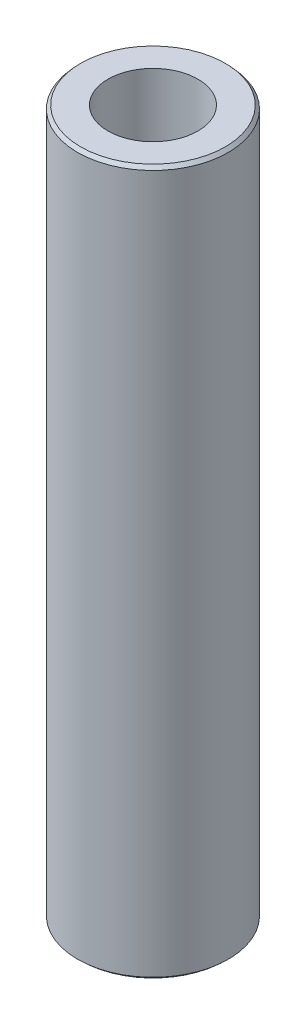
SolidWorks part; units mm, degrees
ref_plane "Front Plane" through (0, 0, 0) normal (0, 0, 1) x (1, 0, 0)
ref_plane "Top Plane" through (0, 0, 0) normal (0, 1, 0) x (1, 0, 0)
ref_plane "Right Plane" through (0, 0, 0) normal (1, 0, 0) x (0, 0, -1)
sketch "Sketch1" plane through (0, 0, 0) normal (0, 1, 0) x (1, 0, 0)
  circle A0 centre (0, 0) radius 15
  dimension "SHAFT_OD" = 30
extrude "Boss-Extrude1" add sketch "Sketch1" along normal blind 140.3058
sketch "Sketch2" plane through (0, 0, 0) normal (0, 1, 0) x (1, 0, 0)
  circle A0 centre (0, 0) radius 8.9473
  dimension "BORE_D" = 17.8947
extrude "Cut-Extrude1" cut sketch "Sketch2" along normal through all
chamfer "Chamfer1" distance 0.6684 angle 41.955 2 edges at (0, 140.3058, 15) (0, 0, 15) first distance on face at (0, 140.3058, 15) first distance on face at (0, 0, 8.9473)
